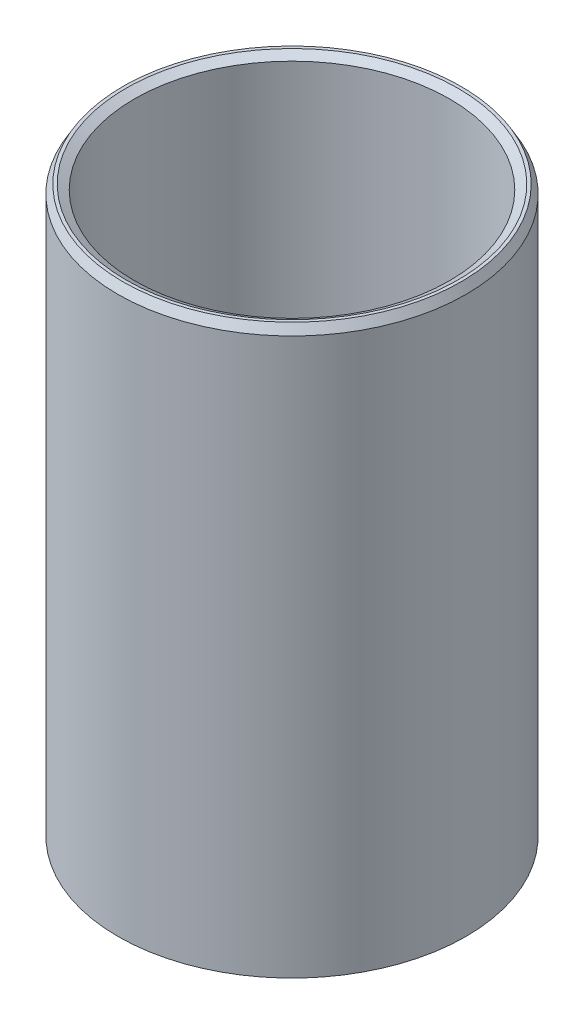
SolidWorks part; units mm, degrees
ref_plane "Front Plane" through (0, 0, 0) normal (0, 0, 1) x (1, 0, 0)
ref_plane "Top Plane" through (0, 0, 0) normal (0, 1, 0) x (1, 0, 0)
ref_plane "Right Plane" through (0, 0, 0) normal (1, 0, 0) x (0, 0, -1)
sketch "Sketch1" plane through (0, 0, 0) normal (0, 1, 0) x (1, 0, 0)
  circle A0 centre (0, 0) radius 52.5
  dimension "SLEEVE_OD" = 105
extrude "Boss-Extrude1" add sketch "Sketch1" along normal blind 171.7616
sketch "Sketch2" plane through (0, 0, 0) normal (0, 1, 0) x (1, 0, 0)
  circle A0 centre (0, 0) radius 47.5187
  dimension "BORE_D" = 95.0374
extrude "Cut-Extrude1" cut sketch "Sketch2" along normal through all
chamfer "Chamfer1" distance 2.5631 angle 30 4 edges at (0, 171.7616, 47.5187) (0, 0, 47.5187) (0, 0, 52.5) (0, 171.7616, 52.5) first distance on face at (0, 171.7616, 47.5187) first distance on face at (0, 0, 47.5187) first distance on face at (0, 171.7616, 52.5)
